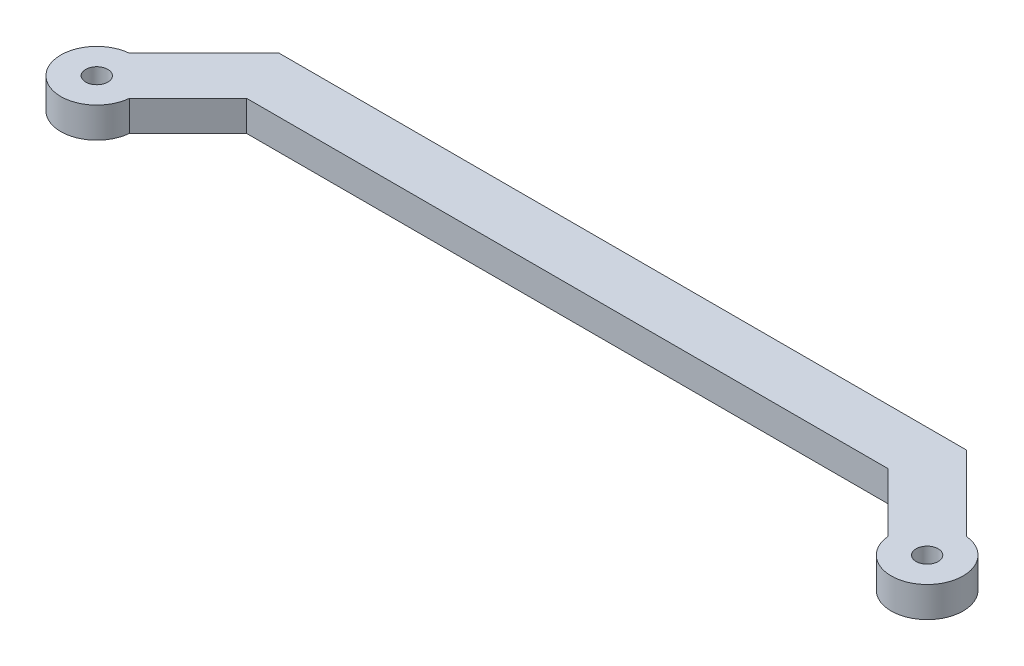
SolidWorks part; units mm, degrees
ref_plane "Plan de face" through (0, 0, 0) normal (0, 0, 1) x (1, 0, 0)
ref_plane "Plan de dessus" through (0, 0, 0) normal (0, 1, 0) x (1, 0, 0)
ref_plane "Plan de droite" through (0, 0, 0) normal (1, 0, 0) x (0, 0, -1)
sketch "Sketch1" plane through (0, 0, 0) normal (0, 1, 0) x (1, 0, 0)
  line L0 (75, -10) -> (60, 5) construction
  line L1 (60, 5) -> (-60, 5) construction
  line L2 (0, 5) -> (0, 0) construction
  line L3 (-57.9289, 0) -> (57.9289, 0)
  line L5 (62.0711, 10) -> (-62.0711, 10)
  line L6 (0, 5) -> (0, 0)
  line L7 (57.9289, 0) -> (68.5276, -10.5987)
  line L8 (62.0711, 10) -> (75.5987, -3.5276)
  line L9 (-75, -10) -> (-60, 5) construction
  line L10 (-62.0711, 10) -> (-75.5987, -3.5276)
  line L11 (-57.9289, 0) -> (-68.5276, -10.5987)
  arc A0 (68.5276, -10.5987) -> (75.5987, -3.5276) centre (75, -10) ccw
  circle A1 centre (75, -10) radius 2
  circle A2 centre (-75, -10) radius 2
  arc A3 (-68.5276, -10.5987) -> (-75.5987, -3.5276) centre (-75, -10) cw
  dimension "D5" = 13
  dimension "D6" = 4
  dimension "D1" = 135
  dimension "D3" = 15
  dimension "D4" = 5
  dimension "D7" = 10
  dimension "D10" = 5
  dimension "D8" = 10
  dimension "D2" = 150
extrude "Boss-Extrude1" add sketch "Sketch1" along normal blind 5.5 contours L3 L7 A0 L8 L5 L10 A3 L11 | A2 | A1
equation "\"D10@Sketch1\"=\"D7@Sketch1\"/2"
equation "\"Longueur1\"= 150mm"
equation "\"Longueur2\"= 175mm"
equation "\"D2@Sketch1\"=\"Longueur1\""
